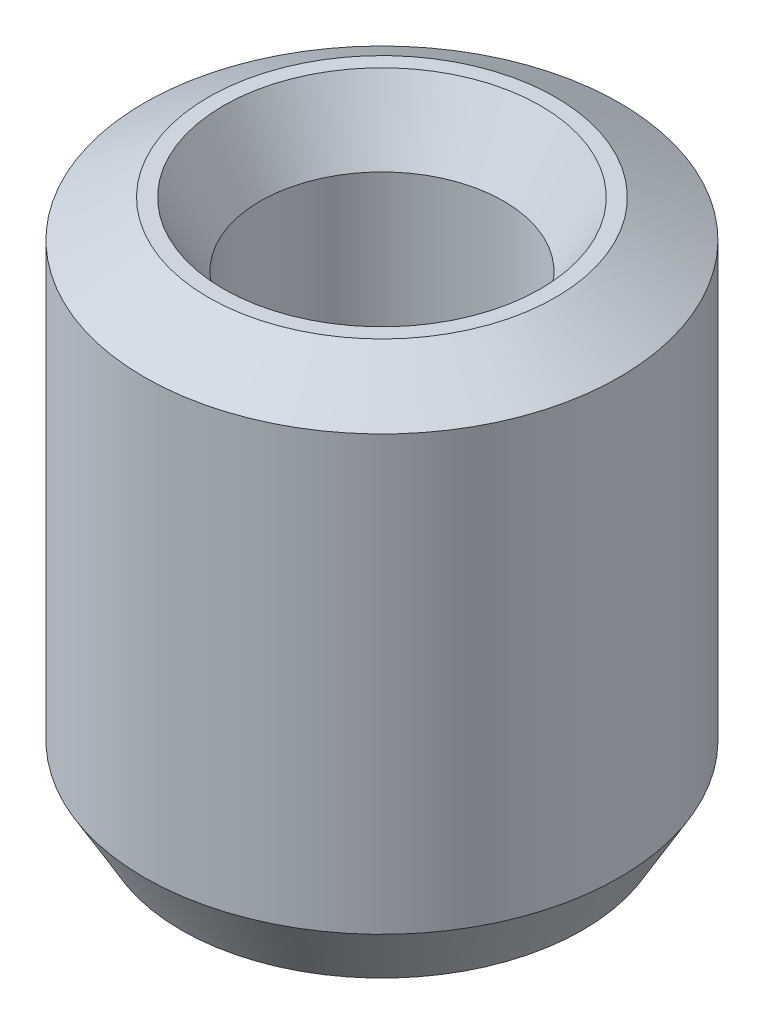
SolidWorks part; units mm, degrees
ref_plane "Front Plane" through (0, 0, 0) normal (0, 0, 1) x (1, 0, 0)
ref_plane "Top Plane" through (0, 0, 0) normal (0, 1, 0) x (1, 0, 0)
ref_plane "Right Plane" through (0, 0, 0) normal (1, 0, 0) x (0, 0, -1)
sketch "Sketch1" plane through (0, 0, 0) normal (0, 1, 0) x (1, 0, 0)
  circle A0 centre (0, 0) radius 20
  dimension "SLEEVE_OD" = 40
extrude "Boss-Extrude1" add sketch "Sketch1" along normal blind 44.9815
sketch "Sketch2" plane through (0, 0, 0) normal (0, 1, 0) x (1, 0, 0)
  circle A0 centre (0, 0) radius 10.2413
  dimension "BORE_D" = 20.4826
extrude "Cut-Extrude1" cut sketch "Sketch2" along normal through all
chamfer "Chamfer1" distance 3.1124 angle 60 4 edges at (0, 44.9815, 10.2413) (0, 0, 10.2413) (0, 0, 20) (0, 44.9815, 20) first distance on face at (0, 44.9815, 10.2413) first distance on face at (0, 0, 10.2413) first distance on face at (0, 44.9815, 20)
